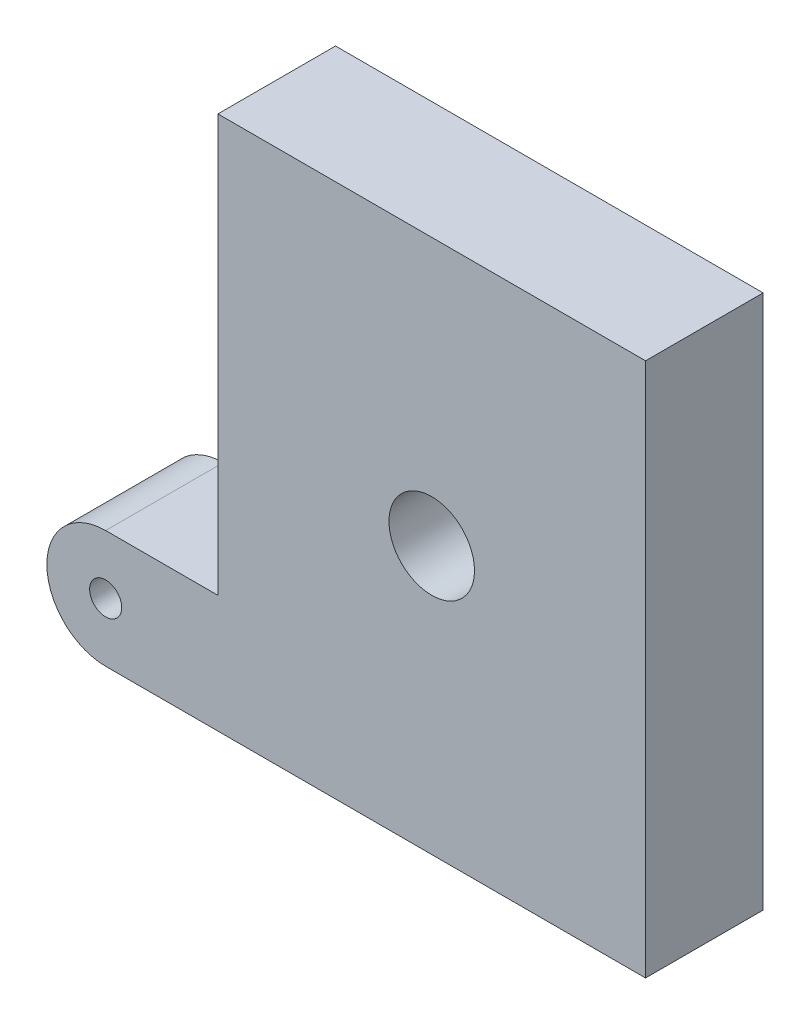
SolidWorks part; units mm, degrees
ref_plane "Plan de face" through (0, 0, 0) normal (0, 0, 1) x (1, 0, 0)
ref_plane "Plan de dessus" through (0, 0, 0) normal (0, 1, 0) x (1, 0, 0)
ref_plane "Plan de droite" through (0, 0, 0) normal (1, 0, 0) x (0, 0, -1)
sketch "Esquisse1" plane through (0, 0, 0) normal (0, 0, 1) x (1, 0, 0)
  line L0 (50.5, 50) -> (-29.5, 50)
  line L1 (-50.5, -50) -> (50.5, -50)
  line L3 (-50.5, 50) -> (50.5, 50) construction
  line L4 (50.5, -50) -> (50.5, 50)
  line L5 (-50.5, -50) -> (50.5, 50) construction
  line L6 (-50.5, 50) -> (50.5, -50) construction
  line L7 (-29.5, 50) -> (-29.5, -28)
  line L8 (-29.5, -28) -> (-50.5, -28)
  arc A0 (-50.5, -50) -> (-50.5, -28) centre (-50.5, -39) cw
  circle A1 centre (10.5, 0) radius 8
  circle A2 centre (-50.5, -39) radius 3
  point P0 (0, 0)
  dimension "D6" = 16
  dimension "D7" = 50
  dimension "D8" = 40
  dimension "D9" = 6
  dimension "D5" = 11
  dimension "D1" = 101
  dimension "D2" = 100
  dimension "D3" = 80
  dimension "D4" = 78
  dimension "D10" = 101
extrude "Boss.-Extru.1" add sketch "Esquisse1" along normal blind 22 contours L7 L8 A0 L1 L4 L0
extrude "Enlèv. mat.-Extru.1" cut sketch "Esquisse1<8>" along normal blind 22 contours A1
sketch "Esquisse1<8>" plane through (0, 0, 0) normal (0, 0, 1) x (1, 0, 0) same geometry as "Esquisse1"
extrude "Enlèv. mat.-Extru.2" cut sketch "Esquisse1<9>" along normal blind 22 contours A2
sketch "Esquisse1<9>" plane through (0, 0, 0) normal (0, 0, 1) x (1, 0, 0) same geometry as "Esquisse1"
